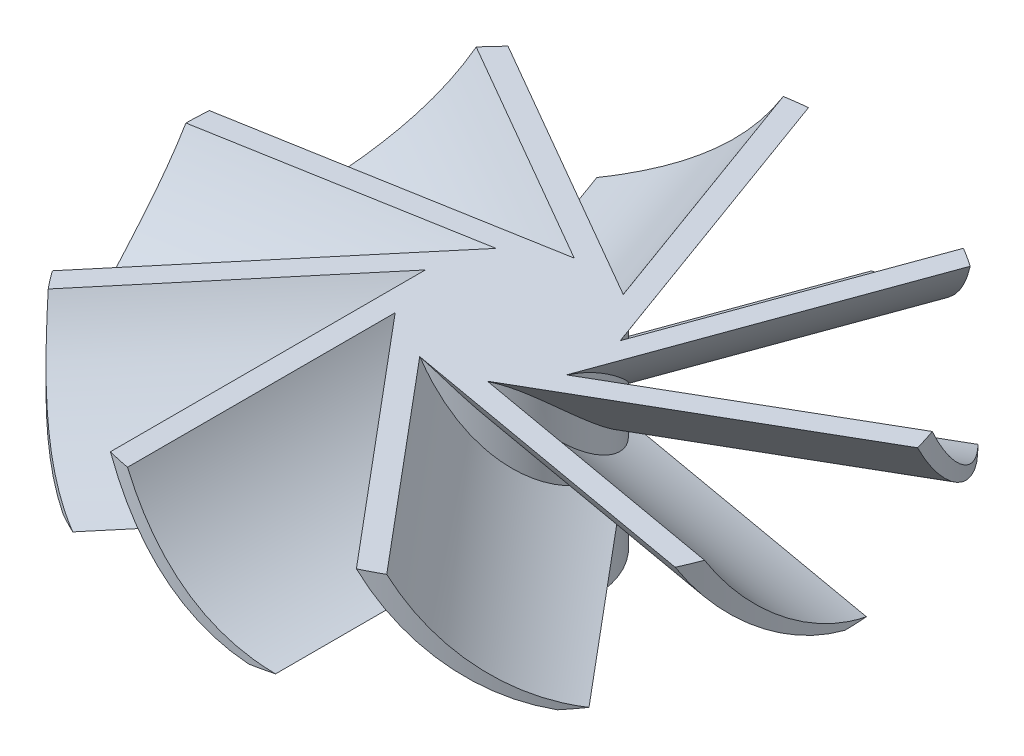
SolidWorks part; units mm, degrees
ref_plane "Front Plane" through (0, 0, 0) normal (0, 0, 1) x (1, 0, 0)
ref_plane "Top Plane" through (0, 0, 0) normal (0, 1, 0) x (1, 0, 0)
ref_plane "Right Plane" through (0, 0, 0) normal (1, 0, 0) x (0, 0, -1)
sketch "Sketch1" plane through (0, 0, 0) normal (0, 1, 0) x (1, 0, 0)
  circle A0 centre (0, 0) radius 7.5
  dimension "D1" = 15
extrude "Boss-Extrude1" add sketch "Sketch1" along normal blind 5 and the other way blind 5
sketch "Sketch2" plane through (0, 0, 0) normal (0, 0, 1) x (1, 0, 0)
  line L0 (7.5, 5) -> (-7.5, 5) construction
  line L2 (-7.5161, 5) -> (-1.7426, -5) construction
  line L3 (-7.5, 5) -> (7.5, 5) construction
  line L4 (-7.5, -5) -> (-7.5, 5) construction
  line L5 (-7.5, -5) -> (7.5, -5) construction
  line L6 (-7.5, 5) -> (-7.5, -5) construction
  line L7 (-7.5, -5) -> (7.5, -5) construction
  line L8 (11.0711, 15.7313) -> (13.0711, 15.7313) construction
  line L9 (-7.5161, 5) -> (-5.5161, 5)
  line L12 (-7.5, 5) -> (-7.5, -5) construction
  line L13 (-7.5161, 5) -> (-7.5161, -5) construction
  line L14 (-7.5161, 0) -> (7.5161, 0) construction
  line L15 (7.5161, 5) -> (7.5161, -5) construction
  line L16 (-7.5, -1.5123) -> (5.5161, -5) construction
  line L19 (5.5161, -5) -> (7.5161, -5)
  arc A0 (-7.5161, 5) -> (5.5161, -5) centre (11.0711, 15.7313) ccw
  arc A1 (-5.5161, 5) -> (7.5161, -5) centre (13.0711, 15.7313) ccw
  point P0 (-7.5, -1.5124)
  point P24 (0, 0)
  point P27 (0, 0)
  dimension "D4" = 2
  dimension "D1" = 15
  dimension "D3" = 60
  dimension "D6" = 15.0323
  dimension "D5" = 2
extrude "Boss-Extrude2" add sketch "Sketch2" along normal blind 45 contours A1 L19 A0 L9
sketch "Sketch3" plane through (0, 0, 0) normal (0, 0, 1) x (1, 0, 0)
  line L0 (0, 0) -> (0, 49.4452) construction
pattern_circular "CirPattern1" count 9 every 40 about axis through (0, 0, 0) along (0, 1, 0) of "Boss-Extrude2"
sketch "Sketch4" plane through (0, 5, 0) normal (0, 1, 0) x (1, 0, 0)
  circle A0 centre (0, 0) radius 30
  circle A1 centre (0, 0) radius 130
  dimension "D1" = 100
  dimension "D2" = 60
extrude "Cut-Extrude1" cut sketch "Sketch4" against normal blind 45
sketch "Sketch5" plane through (0, -5, 0) normal (0, -1, 0) x (1, 0, 0)
  circle A0 centre (0, 0) radius 7.5
  dimension "D1" = 15
extrude "Boss-Extrude3" add sketch "Sketch5" along normal blind 8.4
sketch "Sketch8" plane through (0, -13.4, 0) normal (0, -1, 0) x (1, 0, 0)
  line L0 (-2.5, 0) -> (2.5, 0) construction
  line L1 (-4.6, 3.2) -> (-2.5, 3.2)
  line L2 (-4.6, 3.2) -> (-4.6, -3.2)
  line L3 (-4.6, -3.2) -> (-2.5, -3.2)
  line L4 (-2.5, 3.2) -> (-2.5, -3.2)
  line L5 (0, 0) -> (0, 7.5) construction
  line L6 (2.5, 3.25) -> (2.5, -3.25)
  line L9 (4.6, 3.25) -> (4.6, -3.25)
  line L10 (-0.625, -0.995) -> (-0.625, 0.995)
  line L11 (2.5, 3.25) -> (4.6, 3.25)
  line L12 (2.5, -3.25) -> (4.6, -3.25)
  circle A0 centre (0, 0) radius 7.5 construction
  arc A1 (0.9212, 7.4432) -> (-5.9854, -4.5194) centre (0, 0) ccw construction
  arc A2 (-0.625, -0.995) -> (-0.625, 0.995) centre (0, 0) ccw
  point P7 (5.2458, -4.3133)
  point P9 (0, 0)
  point P11 (2.5, 0)
  point P20 (1.175, 0)
  dimension "D4" = 2.35
  dimension "D1" = 2.1
  dimension "D2" = 6.4
  dimension "D5" = 1.8
  dimension "D6" = 2.5
  dimension "D7" = 2.1
  dimension "D8" = 6.5
extrude "Cut-Extrude2" cut sketch "Sketch8" against normal blind 6.35
sketch "Sketch10" plane through (0, 0, 0) normal (1, 0, 0) x (0, 0, -1)
  line L0 (0, 0) -> (0, -9.533) construction
  line L1 (-7.5, -13.4) -> (7.5, -13.4) construction
  line L2 (0, -10.225) -> (-3.175, -7.05) construction
  line L3 (-3.175, -13.4) -> (3.175, -13.4) construction
  line L4 (-3.175, -13.4) -> (-3.175, -7.05) construction
  line L5 (-3.175, -7.05) -> (3.175, -7.05) construction
  line L6 (3.175, -13.4) -> (3.175, -7.05) construction
  line L7 (-3.175, -13.4) -> (0, -10.225) construction
  circle A0 centre (0, -10.225) radius 1.9
  point P4 (0, -7.05)
  dimension "D2" = 3.8
  dimension "D3" = 6.35
extrude "Cut-Extrude3" cut sketch "Sketch10" against normal blind 8.4 and the other way blind 8.4
